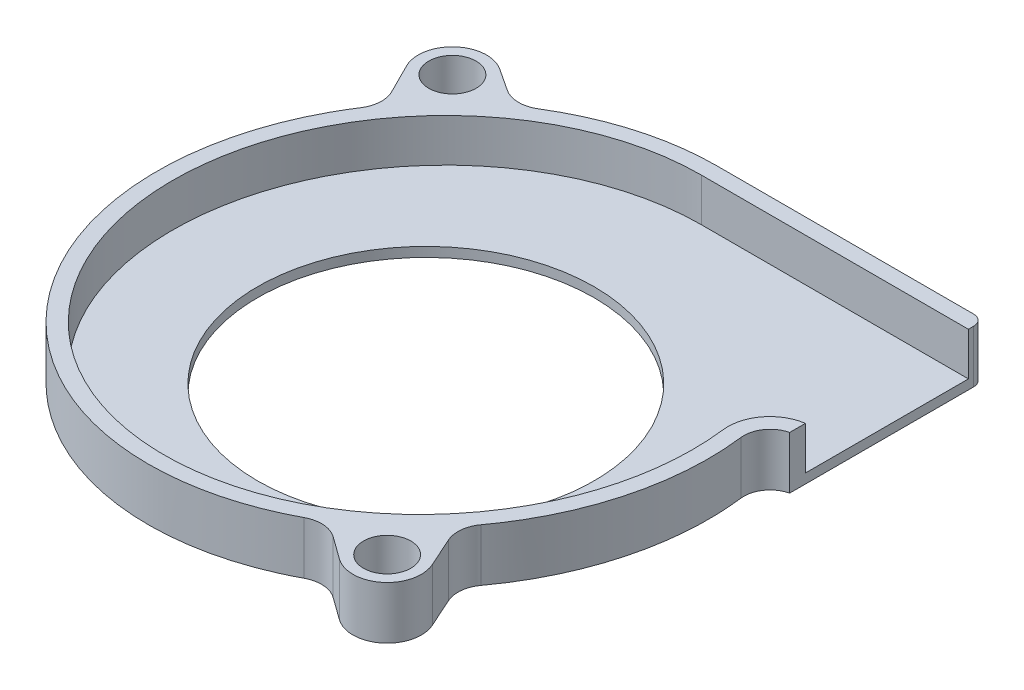
SolidWorks part; units mm, degrees
ref_plane "Front Plane" through (0, 0, 0) normal (0, 0, 1) x (1, 0, 0)
ref_plane "Top Plane" through (0, 0, 0) normal (0, 1, 0) x (1, 0, 0)
ref_plane "Right Plane" through (0, 0, 0) normal (1, 0, 0) x (0, 0, -1)
sketch "Sketch19" plane through (101.6679, 0, -9.2414) normal (0, 1, 0) x (-1, 0, 0)
  line L180 (73.5095, 9.2414) -> (95.2051, 9.2414)
  line L186 (79.9167, 11.9238) -> (79.5136, 11.896)
  line L187 (82.3906, 14.2171) -> (82.2795, 13.8418)
  line L188 (79.5136, 11.896) -> (76.2336, 11.896)
  line L189 (108.1308, 9.2414) -> (129.8264, 9.2414)
  line L190 (99.5137, 9.2414) -> (103.8222, 9.2414)
  line L191 (101.6679, 8.6855) -> (101.6679, 12.994)
  line L192 (101.6679, -18.9032) -> (101.6679, 4.3769)
  line L193 (88.3531, 30.395) -> (88.3531, 32.4937)
  line L194 (88.3531, 29.1024) -> (88.3531, 29.7557)
  line L195 (88.3531, 26.3644) -> (88.3531, 28.4631)
  line L196 (89.326, 29.4221) -> (91.4108, 29.4221)
  line L197 (88.0335, 29.4221) -> (88.6728, 29.4221)
  line L198 (85.2954, 29.4221) -> (87.3802, 29.4221)
  line L199 (117.3872, -12.6488) -> (117.3872, -10.5501)
  line L200 (117.3872, -13.9414) -> (117.3872, -13.2882)
  line L201 (117.3872, -16.6794) -> (117.3872, -14.5807)
  line L202 (118.3462, -13.6217) -> (120.4449, -13.6217)
  line L203 (117.0536, -13.6217) -> (117.7069, -13.6217)
  line L204 (114.3156, -13.6217) -> (116.4143, -13.6217)
  line L205 (100.3893, 23.6264) -> (100.3198, 24.2935)
  line L206 (98.8882, 23.4179) -> (98.7492, 24.0712)
  line L207 (97.4289, 23.0427) -> (97.2204, 23.682)
  line L208 (96.0112, 22.5284) -> (95.7333, 23.14)
  line L209 (94.6492, 21.8613) -> (94.3156, 22.445)
  line L210 (93.3705, 21.0552) -> (92.9674, 21.5972)
  line L211 (92.1752, 20.124) -> (91.7305, 20.6243)
  line L212 (91.0911, 19.0677) -> (90.5908, 19.5263)
  line L213 (90.1182, 17.9141) -> (89.5762, 18.3033)
  line L214 (89.2843, 16.6632) -> (88.7006, 16.9968)
  line L215 (88.5755, 15.329) -> (87.964, 15.593)
  line L216 (88.0057, 13.9252) -> (87.3802, 14.1337)
  line L217 (87.6026, 12.4659) -> (86.9494, 12.6049)
  line L218 (87.3385, 10.9787) -> (86.6714, 11.0482)
  line L219 (87.2412, 9.4777) -> (86.5602, 9.4777)
  line L220 (87.2968, 7.9627) -> (86.6297, 7.8932)
  line L221 (87.5053, 6.4617) -> (86.8521, 6.3227)
  line L222 (87.8667, 5.0023) -> (87.2412, 4.7939)
  line L223 (88.3948, 3.5847) -> (87.7833, 3.3067)
  line L224 (89.0619, 2.2226) -> (88.4782, 1.8891)
  line L225 (89.8542, 0.944) -> (89.3121, 0.5548)
  line L226 (90.7854, -0.2374) -> (90.2989, -0.6961)
  line L227 (91.8417, -1.3215) -> (91.3969, -1.8219)
  line L228 (93.0091, -2.2944) -> (92.6061, -2.8364)
  line L229 (94.26, -3.1422) -> (93.9264, -3.726)
  line L230 (95.5943, -3.851) -> (95.3163, -4.4626)
  line L231 (96.998, -4.407) -> (96.7895, -5.0463)
  line L232 (98.4435, -4.8239) -> (98.3045, -5.4772)
  line L233 (99.9306, -5.088) -> (99.8611, -5.7551)
  line L234 (101.4456, -5.1853) -> (101.4456, -5.8524)
  line L235 (102.9605, -5.1297) -> (103.03, -5.7968)
  line L236 (104.4476, -4.9212) -> (104.5866, -5.5745)
  line L237 (105.9209, -4.546) -> (106.1294, -5.1853)
  line L238 (107.3385, -4.0317) -> (107.6026, -4.6433)
  line L239 (108.6867, -3.3646) -> (109.0203, -3.9483)
  line L240 (109.9654, -2.5585) -> (110.3684, -3.1005)
  line L241 (111.1606, -1.6273) -> (111.6054, -2.1276)
  line L242 (112.2447, -0.571) -> (112.7451, -1.0296)
  line L243 (113.2176, 0.5826) -> (113.7597, 0.1934)
  line L244 (114.0515, 1.8335) -> (114.6353, 1.4999)
  line L245 (114.7604, 3.1677) -> (115.3719, 2.9037)
  line L246 (115.3302, 4.5715) -> (115.9696, 4.363)
  line L247 (115.7472, 6.0308) -> (116.4004, 5.8918)
  line L248 (115.9973, 7.518) -> (116.6645, 7.4485)
  line L249 (116.1085, 9.019) -> (116.7757, 9.019)
  line L250 (116.0529, 10.534) -> (116.7201, 10.6035)
  line L251 (115.8306, 12.0211) -> (116.4977, 12.174)
  line L252 (115.4692, 13.4944) -> (116.1085, 13.7028)
  line L253 (114.955, 14.912) -> (115.5665, 15.19)
  line L254 (114.2878, 16.2741) -> (114.8577, 16.6076)
  line L255 (113.4817, 17.5527) -> (114.0238, 17.9419)
  line L256 (112.5505, 18.7341) -> (113.0509, 19.1789)
  line L257 (111.4942, 19.8182) -> (111.939, 20.3185)
  line L258 (110.3406, 20.7911) -> (110.7298, 21.3331)
  line L259 (109.0759, 21.6389) -> (109.4233, 22.2088)
  line L260 (107.7416, 22.3477) -> (108.0196, 22.9593)
  line L261 (106.3517, 22.9037) -> (106.5463, 23.543)
  line L262 (104.8924, 23.3206) -> (105.0314, 23.9739)
  line L263 (103.4053, 23.5847) -> (103.4747, 24.2379)
  line L264 (101.8903, 23.682) -> (101.8903, 24.3491)
  line L265 (116.7479, 10.1587) -> (116.7757, 9.2414)
  line L266 (116.6645, 11.0621) -> (116.7479, 10.1587)
  line L267 (116.5255, 11.9655) -> (116.6645, 11.0621)
  line L268 (100.7645, 24.3213) -> (101.6679, 24.3491)
  line L269 (99.8472, 24.2379) -> (100.7645, 24.3213)
  line L270 (86.588, 10.1587) -> (86.6714, 11.0621)
  line L271 (86.5602, 9.2414) -> (86.588, 10.1587)
  line L272 (86.588, 8.338) -> (86.5602, 9.2414)
  line L273 (86.6714, 7.4207) -> (86.588, 8.338)
  line L274 (101.6679, -5.8524) -> (100.7645, -5.8246)
  line L275 (102.5852, -5.8246) -> (101.6679, -5.8524)
  line L276 (116.6645, 7.4207) -> (116.5255, 6.5312)
  line L277 (116.7479, 8.338) -> (116.6645, 7.4207)
  line L278 (116.7757, 9.2414) -> (116.7479, 8.338)
  line L279 (116.0807, 10.117) -> (116.1085, 9.2414)
  line L280 (115.9973, 10.9926) -> (116.0807, 10.117)
  line L281 (115.8723, 11.8543) -> (115.9973, 10.9926)
  line L282 (100.7923, 23.6542) -> (101.6679, 23.682)
  line L283 (99.9306, 23.5708) -> (100.7923, 23.6542)
  line L284 (87.2551, 10.117) -> (87.3385, 10.9926)
  line L285 (87.2273, 9.2414) -> (87.2551, 10.117)
  line L286 (87.2551, 8.3797) -> (87.2273, 9.2414)
  line L287 (87.3385, 7.5041) -> (87.2551, 8.3797)
  line L288 (101.6679, -5.1853) -> (100.7923, -5.1575)
  line L289 (102.5435, -5.1575) -> (101.6679, -5.1853)
  line L290 (115.9973, 7.5041) -> (115.8723, 6.6424)
  line L291 (116.0807, 8.3797) -> (115.9973, 7.5041)
  line L292 (116.1085, 9.2414) -> (116.0807, 8.3797)
  line L293 (111.9668, 9.978) -> (111.9946, 9.2414)
  line L294 (111.8834, 10.7146) -> (111.9668, 9.978)
  line L295 (111.7583, 11.4374) -> (111.8834, 10.7146)
  line L296 (100.9313, 19.5402) -> (101.6679, 19.568)
  line L297 (100.1947, 19.4707) -> (100.9313, 19.5402)
  line L298 (91.3691, 9.978) -> (91.4525, 10.7146)
  line L299 (91.3413, 9.2414) -> (91.3691, 9.978)
  line L300 (91.3691, 8.5048) -> (91.3413, 9.2414)
  line L301 (91.4525, 7.7821) -> (91.3691, 8.5048)
  line L302 (101.6679, -1.0713) -> (100.9313, -1.0435)
  line L303 (102.4046, -1.0435) -> (101.6679, -1.0713)
  line L304 (111.8834, 7.7821) -> (111.7583, 7.0593)
  line L305 (111.9668, 8.5048) -> (111.8834, 7.7821)
  line L306 (111.9946, 9.2414) -> (111.9668, 8.5048)
  line L307 (98.6797, 31.9099) -> (105.8375, 32.2852)
  line L308 (100.5838, 31.4096) -> (100.5561, 32.0211)
  line L309 (103.989, 31.6737) -> (103.9612, 32.1879)
  line L310 (105.8375, 32.2852) -> (105.8792, 31.5903)
  line L311 (98.7214, 31.0482) -> (98.6797, 31.9099)
  line L312 (86.2961, 22.8481) -> (86.9494, 23.682)
  line L313 (82.3906, 14.2171) -> (82.6269, 15.2595)
  line L314 (87.1856, 24.0156) -> (86.9494, 23.682)
  line L315 (86.7131, 27.7265) -> (86.9911, 27.4207)
  line L316 (90.6325, 30.2838) -> (90.3962, 30.6174)
  line L317 (94.2739, 29.436) -> (93.8986, 29.297)
  line L318 (90.1877, 30.9231) -> (90.3962, 30.6174)
  line L319 (86.7131, 27.7265) -> (86.4768, 27.9906)
  line L320 (90.1043, 29.7418) -> (90.1321, 29.4221)
  line L321 (90.0209, 30.0336) -> (90.1043, 29.7418)
  line L322 (86.588, 29.4221) -> (86.6158, 29.7418)
  line L323 (86.6158, 29.1163) -> (86.588, 29.4221)
  line L324 (90.1043, 29.1163) -> (90.0209, 28.8245)
  line L325 (90.1321, 29.4221) -> (90.1043, 29.1163)
  line L326 (115.2051, -14.678) -> (115.4414, -14.9699)
  line L327 (111.7166, -13.997) -> (112.0641, -13.858)
  line L328 (120.153, -7.4091) -> (119.3747, -8.2986)
  line L329 (125.6429, 4.1545) -> (125.3928, 3.0009)
  line L330 (119.1384, -8.5904) -> (119.3747, -8.2986)
  line L331 (119.2357, -12.1485) -> (119.0272, -11.8427)
  line L332 (115.6777, -15.2618) -> (115.4414, -14.9699)
  line L333 (119.2357, -12.1485) -> (119.4442, -12.4681)
  line L334 (119.1245, -13.316) -> (119.1523, -13.6217)
  line L335 (119.0411, -13.0102) -> (119.1245, -13.316)
  line L336 (115.6082, -13.6217) -> (115.636, -13.316)
  line L337 (115.636, -13.9275) -> (115.6082, -13.6217)
  line L338 (119.1245, -13.9275) -> (119.0411, -14.2194)
  line L339 (119.1523, -13.6217) -> (119.1245, -13.9275)
  line L340 (82.9466, 18.4283) -> (81.6262, 13.3137)
  line L341 (82.9883, 16.4825) -> (82.474, 16.6076)
  line L342 (82.5713, 15.0093) -> (82.0988, 15.1344)
  line L343 (81.6262, 13.3137) -> (81.9737, 13.2303)
  line L344 (83.6554, 18.2477) -> (82.9466, 18.4283)
  line L345 (126.6992, 13.411) -> (126.6992, 6.2393)
  line L346 (126.1294, 11.5347) -> (126.6992, 11.5347)
  line L347 (126.1711, 8.1156) -> (126.6992, 8.1156)
  line L348 (126.6992, 6.2393) -> (125.9904, 6.2393)
  line L349 (125.907, 13.411) -> (126.6992, 13.411)
  line L350 (90.7715, -16.5126) -> (83.5998, -16.5126)
  line L351 (88.8952, -16.0262) -> (88.8952, -16.5126)
  line L352 (85.49, -16.0262) -> (85.49, -16.5126)
  line L353 (83.5998, -16.5126) -> (83.5998, -16.0262)
  line L354 (90.7715, -16.0262) -> (90.7715, -16.5126)
  line L355 (119.7222, 25.8224) -> (120.5422, 25.0441)
  line L356 (94.2739, 29.436) -> (95.3163, 29.9086)
  line L357 (76.2336, -15.2479) -> (76.2336, 11.896)
  line L358 (76.2614, -15.4424) -> (76.2336, -15.2479)
  line L359 (76.3309, -15.637) -> (76.2614, -15.4424)
  line L360 (76.456, -15.8038) -> (76.3309, -15.637)
  line L361 (76.6227, -15.9289) -> (76.456, -15.8038)
  line L362 (76.8173, -15.9984) -> (76.6227, -15.9289)
  line L363 (77.0119, -16.0262) -> (76.8173, -15.9984)
  line L364 (103.7666, -16.0262) -> (77.0119, -16.0262)
  line L365 (104.6283, -15.9984) -> (103.7666, -16.0262)
  line L366 (105.49, -15.9289) -> (104.6283, -15.9984)
  line L367 (110.7854, -14.4278) -> (109.8264, -14.817)
  line L368 (111.7166, -13.997) -> (110.7854, -14.4278)
  line L369 (125.8514, 5.2664) -> (125.6429, 4.1545)
  line L370 (120.5422, 25.0441) -> (121.1676, 24.3908)
  spline S28 degree 3 poles (82.2795, 13.8418) (82.1213, 13.5208) (81.8076, 12.8842) (80.9543, 12.1818) (80.2645, 12.0103) (79.9167, 11.9238) knots 0 0 0 0 0.335193 0.664797 1 1 1 1
  spline S29 degree 3 poles (101.6679, 24.3491) (104.0069, 24.0252) (108.6295, 23.3848) (114.3269, 18.6424) (115.7868, 14.2088) (116.5255, 11.9655) knots 0 0 0 0 0.335972 0.664018 1 1 1 1
  spline S30 degree 3 poles (86.6714, 11.0621) (87.2366, 13.2458) (88.355, 17.5661) (93.3409, 22.5601) (97.6629, 23.6747) (99.8472, 24.2379) knots 0 0 0 0 0.335761 0.664295 1 1 1 1
  spline S31 degree 3 poles (100.7645, -5.8246) (98.4503, -5.3637) (93.8723, -4.4518) (88.48, 0.6318) (87.2787, 5.141) (86.6714, 7.4207) knots 0 0 0 0 0.335739 0.664168 1 1 1 1
  spline S32 degree 3 poles (116.5255, 6.5312) (115.8334, 4.3849) (114.4633, 0.1363) (109.1811, -4.5461) (104.7988, -5.3956) (102.5852, -5.8246) knots 0 0 0 0 0.335641 0.664413 1 1 1 1
  spline S33 degree 3 poles (101.6679, 23.682) (103.9054, 23.3721) (108.3203, 22.7605) (113.7584, 18.2278) (115.1613, 13.998) (115.8723, 11.8543) knots 0 0 0 0 0.336336 0.663662 1 1 1 1
  spline S34 degree 3 poles (87.3385, 10.9926) (87.8783, 13.0779) (88.947, 17.2069) (93.7146, 21.9749) (97.8452, 23.0354) (99.9306, 23.5708) knots 0 0 0 0 0.335633 0.664571 1 1 1 1
  spline S35 degree 3 poles (100.7923, -5.1575) (98.5828, -4.7133) (94.2132, -3.8348) (89.057, 1.0146) (87.9157, 5.3244) (87.3385, 7.5041) knots 0 0 0 0 0.335787 0.664078 1 1 1 1
  spline S36 degree 3 poles (115.8723, 6.6424) (115.2066, 4.5932) (113.8893, 0.5378) (108.8443, -3.9341) (104.6584, -4.7469) (102.5435, -5.1575) knots 0 0 0 0 0.335708 0.664385 1 1 1 1
  spline S37 degree 3 poles (101.6679, 19.568) (103.228, 19.3569) (106.3141, 18.9394) (110.1593, 15.8464) (111.2213, 12.9179) (111.7583, 11.4374) knots 0 0 0 0 0.335769 0.664184 1 1 1 1
  spline S38 degree 3 poles (91.4525, 10.7146) (91.8473, 12.1526) (92.6277, 14.9948) (95.9245, 18.2679) (98.7596, 19.0665) (100.1947, 19.4707) knots 0 0 0 0 0.335838 0.663808 1 1 1 1
  spline S39 degree 3 poles (100.9313, -1.0435) (99.3926, -0.723) (96.3435, -0.0878) (92.7284, 3.2707) (91.8804, 6.2689) (91.4525, 7.7821) knots 0 0 0 0 0.335364 0.664577 1 1 1 1
  spline S40 degree 3 poles (111.7583, 7.0593) (111.2607, 5.6562) (110.2741, 2.8742) (106.7592, -0.1744) (103.8644, -0.7521) (102.4046, -1.0435) knots 0 0 0 0 0.3353 0.664782 1 1 1 1
  spline S41 degree 3 poles (82.6269, 15.2595) (82.9027, 16.1601) (83.4547, 17.963) (84.6972, 20.5167) (85.7635, 22.0714) (86.2961, 22.8481) knots 0 0 0 0 0.333132 0.666848 1 1 1 1
  spline S42 degree 3 poles (86.9911, 27.4207) (87.1995, 27.074) (87.6163, 26.3808) (87.7039, 25.1152) (87.3583, 24.382) (87.1856, 24.0156) knots 0 0 0 0 0.333613 0.667008 1 1 1 1
  spline S43 degree 3 poles (93.8986, 29.297) (93.5019, 29.2146) (92.707, 29.0495) (91.4909, 29.4223) (90.9183, 29.9969) (90.6325, 30.2838) knots 0 0 0 0 0.332897 0.666933 1 1 1 1
  spline S44 degree 3 poles (86.4768, 27.9906) (86.1885, 28.8219) (85.6369, 30.4125) (88.0271, 32.3046) (89.4462, 31.3972) (90.1877, 30.9231) knots 0 0 0 0 0.343302 0.656868 1 1 1 1
  spline S45 degree 3 poles (86.6158, 29.7418) (86.8446, 30.2312) (87.2875, 31.1785) (89.1095, 31.3307) (89.7103, 30.4757) (90.0209, 30.0336) knots 0 0 0 0 0.340481 0.658978 1 1 1 1
  spline S46 degree 3 poles (90.0209, 28.8245) (89.7109, 28.3825) (89.1105, 27.5268) (87.2866, 27.6775) (86.8442, 28.6264) (86.6158, 29.1163) knots 0 0 0 0 0.340673 0.659593 1 1 1 1
  spline S47 degree 3 poles (112.0641, -13.858) (112.441, -13.7794) (113.1871, -13.6238) (114.3407, -13.9227) (114.915, -14.4245) (115.2051, -14.678) knots 0 0 0 0 0.335636 0.664286 1 1 1 1
  spline S48 degree 3 poles (125.3928, 3.0009) (125.0296, 1.749) (124.3006, -0.7644) (122.5332, -4.2934) (120.9444, -6.3732) (120.153, -7.4091) knots 0 0 0 0 0.332521 0.667547 1 1 1 1
  spline S49 degree 3 poles (119.0272, -11.8427) (118.8653, -11.4887) (118.5486, -10.7962) (118.5971, -9.6046) (118.9553, -8.9336) (119.1384, -8.5904) knots 0 0 0 0 0.338158 0.661533 1 1 1 1
  spline S50 degree 3 poles (119.4442, -12.4681) (119.6189, -13.254) (119.9552, -14.7658) (117.7357, -16.4106) (116.3823, -15.6551) (115.6777, -15.2618) knots 0 0 0 0 0.341627 0.657242 1 1 1 1
  spline S51 degree 3 poles (115.636, -13.316) (115.865, -12.8234) (116.3062, -11.8746) (118.1297, -11.7064) (118.7298, -12.5648) (119.0411, -13.0102) knots 0 0 0 0 0.341897 0.65855 1 1 1 1
  spline S52 degree 3 poles (119.0411, -14.2194) (118.7323, -14.663) (118.1357, -15.52) (116.3165, -15.3612) (115.8684, -14.4173) (115.636, -13.9275) knots 0 0 0 0 0.340624 0.657859 1 1 1 1
  spline S53 degree 3 poles (95.3163, 29.9086) (98.1066, 30.7198) (103.6867, 32.3422) (112.6245, 30.9005) (117.3564, 27.515) (119.7222, 25.8224) knots 0 0 0 0 0.333391 0.66672 1 1 1 1
  spline S54 degree 3 poles (109.8264, -14.817) (109.3624, -14.9921) (108.4256, -15.3457) (106.9748, -15.7324) (105.9817, -15.8638) (105.49, -15.9289) knots 0 0 0 0 0.331237 0.668901 1 1 1 1
  spline S55 degree 3 poles (121.1676, 24.3908) (122.4335, 22.5329) (124.9882, 18.7834) (126.4142, 12.0045) (126.0381, 7.5014) (125.8514, 5.2664) knots 0 0 0 0 0.330973 0.667942 1 1 1 1
sketch "Sketch18" plane through (0, 0, 0) normal (0, 1, 0) x (1, 0, 0)
  line L0 (-23.0057, 21.1739) -> (-21.5825, 18.3332)
  line L1 (14.4232, -22.6366) -> (12.2821, -21.0936)
  line L2 (-18.3115, 25.3434) -> (-16.2051, 23.9551)
  line L3 (-16.9421, 19.0744) -> (0, 0) construction
  line L4 (16.3234, -20) -> (0, 0) construction
  line L5 (-33.0815, -23.9) -> (4.114, -23.9) construction
  line L6 (-26.2, -10.7544) -> (-26.2, -0.8211) construction
  line L7 (0, 0) -> (0, -6.8242) construction
  line L8 (-4, 0) -> (-4, -27.6209) construction
  line L9 (4, 0) -> (4, -27.6209) construction
  line L10 (0, 0) -> (0, 25.466) construction
  line L11 (0.75, 0) -> (0.75, 25.466) construction
  line L12 (-0.75, 0) -> (-0.75, 25.466) construction
  line L13 (-12.8119, -19.8447) -> (10.3119, 23.6447) construction
  line L14 (-21.6522, 12.748) -> (19.1522, -8.948) construction
  line L15 (-1.25, 1.9) -> (3.3669, 1.9) construction
  line L16 (0, 0) -> (21.8429, 12.611) construction
  line L17 (0, 0) -> (-26.1434, 15.0939) construction
  line L18 (0, 0) -> (-23.531, -13.5856) construction
  line L19 (-0.0106, 27.7) -> (24.4, 27.7)
  line L20 (0, 0) -> (22.2135, -12.825) construction
  line L21 (0, 0) -> (6.1332, 0) construction
  line L22 (4, 0) -> (4, -6.8242) construction
  line L23 (-4, 0) -> (-4, -6.8242) construction
  line L24 (-1.5, 0) -> (-26.5184, 14.4444) construction
  line L25 (-1.5, 0) -> (-23.906, -12.9361) construction
  line L26 (25.4, 26.7) -> (25.4, 9.2)
  line L27 (25.4, 9.2) -> (23.0016, 9.2)
  line L28 (1.5, 0) -> (-25.7684, 15.7434) construction
  line L29 (1.5, 0) -> (-23.156, -14.2351) construction
  line L30 (9.3582, -4.5369) -> (22.5885, -12.1755) construction
  line L31 (19.2873, -18.6667) -> (18.0311, -15.874)
  line L157 (8.6082, -5.836) -> (21.8385, -13.4745) construction
  line L159 (9.3582, 4.5369) -> (22.2179, 11.9615) construction
  line L161 (8.6082, 5.836) -> (21.4679, 13.2605) construction
  line L164 (11.0633, 27.6622) -> (11.0633, 28.1486) construction
  line L165 (18.2349, 28.1486) -> (18.2349, 27.6622) construction
  line L166 (16.3586, 27.6622) -> (16.3586, 28.1486) construction
  line L167 (12.9535, 27.6622) -> (12.9535, 28.1486) construction
  line L168 (11.0633, 28.1486) -> (18.2349, 28.1486) construction
  line L169 (-26.0052, -3.975) -> (-26.3506, -3.975) construction
  line L170 (-26.3506, 3.1828) -> (-25.7716, 3.1828) construction
  line L171 (-26.1178, 1.3065) -> (-26.3506, 1.3065) construction
  line L172 (-26.0193, -2.0987) -> (-26.3506, -2.0987) construction
  line L173 (-26.3506, -3.975) -> (-26.3506, 3.1828) construction
  line L174 (19.9063, -12.0569) -> (20.36, -12.2293) construction
  line L175 (22.6116, -6.1418) -> (22.2945, -6.0236) construction
  line L176 (21.4807, -7.7289) -> (21.9583, -7.9069) construction
  line L177 (20.6345, -10.3321) -> (21.0132, -10.4642) construction
  line L178 (20.36, -12.2293) -> (22.6116, -6.1418) construction
  circle A0 centre (16.3234, -20) radius 2.25
  arc A1 (19.2873, -18.6667) -> (14.4232, -22.6366) centre (16.3234, -20) ccw construction
  circle A2 centre (-20.1, 22.6298) radius 2.25
  arc A3 (-18.3115, 25.3434) -> (-23.0057, 21.1739) centre (-20.1, 22.6298) ccw
  circle A4 centre (0, 0) radius 9.2 construction
  arc A5 (-16.2051, 23.9551) -> (-13.1979, 23.9077) centre (-14.6643, 26.293) ccw
  arc A6 (-21.5825, 18.3332) -> (-21.7386, 15.5524) centre (-24.0858, 17.079) cw
  arc A7 (-23.0057, 21.1739) -> (-18.3115, 25.3434) centre (-20.1, 22.6298) ccw construction
  arc A8 (12.2821, -21.0936) -> (9.3249, -20.8959) centre (10.6451, -23.3651) ccw
  arc A9 (25.4, 26.7) -> (24.4, 27.7) centre (24.4, 26.7) ccw
  circle A10 centre (0, 0) radius 10.4 construction
  arc A11 (18.0311, -15.874) -> (18.3294, -13.0658) centre (20.5846, -14.7253) cw
  arc A12 (14.4232, -22.6366) -> (19.2873, -18.6667) centre (16.3234, -20) ccw
  circle A13 centre (0, 0) radius 16
  ellipse E0 centre (-1.25, 1.9) end of major axis (10.3119, 23.6447) minor radius 23.1069 construction
  ellipse E1 centre (-1.25, 1.9) end of major axis (-13.5161, -21.1691) minor radius 24.6069 (-21.7386, 15.5524) -> (9.3249, -20.8959) ccw
  ellipse E2 centre (-1.25, 1.9) end of major axis (-13.5161, -21.1691) minor radius 24.6069 (-0.0106, 27.7) -> (-13.1979, 23.9077) ccw
  ellipse E3 centre (-1.25, 1.9) end of major axis (-13.5161, -21.1691) minor radius 24.6069 (23.0016, 9.2) -> (-0.0106, 27.7) ccw construction
  ellipse E4 centre (-1.25, 1.9) end of major axis (-13.5161, -21.1691) minor radius 24.6069 (18.3294, -13.0658) -> (23.0016, 9.2) ccw
  dimension "D1" = 6.5
  dimension "D2" = 4.5
  dimension "D4" = 32
  dimension "D5" = 2.8
  dimension "D7" = 0.75
  dimension "D8" = 1
  dimension "D16" = 18.4
  dimension "D34" = 15
  dimension "D6" = 15
  dimension "D9" = 16.3234
  dimension "D10" = 20.1
  dimension "D11" = 25.4
  dimension "D12" = 27.7
  dimension "D13" = 51.6
  dimension "D14" = 20
  dimension "D15" = 51.6
  dimension "D21" = 17.5
  dimension "D22" = 28
  dimension "D23" = 0.75
  dimension "D24" = 1.9
  dimension "D25" = 1.25
  dimension "D26" = 1.5
  dimension "D27" = 1.5
  dimension "D28" = 30
  dimension "D29" = 30
  dimension "D30" = 30
  dimension "D31" = 30
  dimension "D33" = 48.388
  dimension "D17" = 4
  dimension "D18" = 4
  dimension "D19" = 1.2
  dimension "D20" = 0.75
  dimension "D32" = 0.75
extrude "Boss-Extrude2" add sketch "Sketch18" along normal blind 0.91
fillet "Fillet1" radius 2.5 1 edges at (23.0016, 0.455, -9.2)
sketch "Sketch22" plane through (0, 0.91, 0) normal (0, -1, 0) x (-1, 0, 0)
  line L0 (0.0106, 27.7) -> (-24.4, 27.7) construction
  line L1 (-25.4, 26.7) -> (-25.4, 9.2) construction
  line L3 (-19.2873, -18.6667) -> (-18.0311, -15.874) construction
  line L4 (-23.0016, 9.2) -> (-18.3294, -13.0658) construction
  line L5 (-21.7837, 10.7) -> (-16.9208, -12.4744) construction
  line L6 (13.1979, 23.9077) -> (0.0106, 27.7) construction
  line L7 (12.608, 22.5165) -> (-0.2008, 26.2) construction
  line L8 (-9.3249, -20.8959) -> (21.7386, 15.5524) construction
  line L9 (-9.8059, -19.1478) -> (19.98, 15.8015) construction
  line L10 (-25.4, 9.2) -> (-23.0016, 9.2) construction
  line L13 (-14.4232, -22.6366) -> (-12.2821, -21.0936) construction
  line L14 (23.0057, 21.1739) -> (21.5825, 18.3332) construction
  line L15 (18.3115, 25.3434) -> (16.2051, 23.9551) construction
  line L16 (0.0106, 27.7) -> (-24.4, 27.7)
  line L17 (-25.4, 26.7) -> (-25.4, 26.2)
  line L20 (-19.2873, -18.6667) -> (-18.0311, -15.874)
  line L21 (-14.4232, -22.6366) -> (-12.2821, -21.0936)
  line L22 (23.0057, 21.1739) -> (21.5825, 18.3332)
  line L23 (18.3115, 25.3434) -> (16.2051, 23.9551)
  line L24 (-25.4, 10.7) -> (-25.4, 9.2)
  line L30 (-0.0142, 26.2) -> (-25.4, 26.2)
  line L31 (-0.2008, 26.2) -> (-23.9, 26.2) construction
  line L32 (-23.9, 26.2) -> (-23.9, 10.7) construction
  line L33 (-23.9, 10.7) -> (-21.7837, 10.7) construction
  line L34 (-25.4, 26.7) -> (-25.4, 9.2) construction
  line L35 (19.137, 24.0909) -> (17.0306, 22.7027) construction
  line L36 (21.6646, 21.8459) -> (20.2414, 19.0052) construction
  line L37 (-17.9194, -19.2821) -> (-16.6631, -16.4894) construction
  line L38 (-15.3002, -21.4197) -> (-13.1592, -19.8767) construction
  arc A1 (-23.4964, 6.4567) -> (-25.4, 9.2) centre (-25.977, 6.7675) ccw construction
  arc A2 (-24.4, 27.7) -> (-25.4, 26.7) centre (-24.4, 26.7) ccw construction
  arc A3 (-18.0311, -15.874) -> (-18.3294, -13.0658) centre (-20.5846, -14.7253) ccw construction
  arc A4 (-19.2873, -18.6667) -> (-14.4232, -22.6366) centre (-16.3234, -20) ccw construction
  arc A5 (-9.3249, -20.8959) -> (-12.2821, -21.0936) centre (-10.6451, -23.3651) ccw construction
  arc A6 (-22.0099, 6.2489) -> (-25.4, 10.7) centre (-25.9793, 6.7422) ccw
  arc A7 (-23.4964, 6.4567) -> (-25.4, 9.2) centre (-25.977, 6.7675) ccw
  arc A15 (21.5825, 18.3332) -> (21.7386, 15.5524) centre (24.0858, 17.079) ccw construction
  arc A16 (23.0057, 21.1739) -> (18.3115, 25.3434) centre (20.1, 22.6298) ccw construction
  arc A17 (13.1979, 23.9077) -> (16.2051, 23.9551) centre (14.6643, 26.293) ccw construction
  arc A18 (-24.4, 27.7) -> (-25.4, 26.7) centre (-24.4, 26.7) ccw
  arc A19 (-18.0311, -15.874) -> (-18.3294, -13.0658) centre (-20.5846, -14.7253) ccw
  arc A20 (-19.2873, -18.6667) -> (-14.4232, -22.6366) centre (-16.3234, -20) ccw
  arc A21 (-9.3249, -20.8959) -> (-12.2821, -21.0936) centre (-10.6451, -23.3651) ccw
  arc A22 (21.5825, 18.3332) -> (21.7386, 15.5524) centre (24.0858, 17.079) ccw
  arc A23 (23.0057, 21.1739) -> (18.3115, 25.3434) centre (20.1, 22.6298) ccw
  arc A24 (13.1979, 23.9077) -> (16.2051, 23.9551) centre (14.6643, 26.293) ccw
  circle A25 centre (20.1, 22.6298) radius 2.25 construction
  arc A32 (-23.9, 26.2) -> (-23.9, 26.2) centre (-23.9, 26.2) ccw construction
  circle A33 centre (20.1, 22.6298) radius 2.25
  circle A34 centre (-16.3234, -20) radius 2.25 construction
  circle A35 centre (-16.3234, -20) radius 2.25
  arc A36 (21.6646, 21.8459) -> (19.137, 24.0909) centre (20.1, 22.6298) ccw construction
  arc A37 (12.608, 22.5165) -> (17.0306, 22.7027) centre (14.6643, 26.293) ccw construction
  arc A38 (20.2414, 19.0052) -> (19.98, 15.8015) centre (24.0858, 17.079) ccw construction
  arc A39 (-16.6631, -16.4894) -> (-16.9208, -12.4744) centre (-20.5846, -14.7253) ccw construction
  arc A40 (-17.9194, -19.2821) -> (-15.3002, -21.4197) centre (-16.3234, -20) ccw construction
  arc A41 (-9.8059, -19.1478) -> (-13.1592, -19.8767) centre (-10.6451, -23.3651) ccw construction
  ellipse E0 centre (1.25, 1.9) end of major axis (-10.3119, 23.6447) minor radius 23.1047 (-22.0099, 6.2489) -> (-0.0142, 26.2) ccw
  ellipse E2 centre (1.25, 1.9) end of major axis (13.5161, -21.1691) minor radius 24.6069 (-23.4964, 6.4567) -> (-18.3294, -13.0658) ccw construction
  ellipse E3 centre (1.25, 1.9) end of major axis (13.5161, -21.1691) minor radius 24.6069 (-23.4964, 6.4567) -> (-18.3294, -13.0658) ccw
  ellipse E5 centre (1.25, 1.9) end of major axis (13.5161, -21.1691) minor radius 24.6069 (-9.3249, -20.8959) -> (21.7386, 15.5524) ccw construction
  ellipse E6 centre (1.25, 1.9) end of major axis (13.5161, -21.1691) minor radius 24.6069 (13.1979, 23.9077) -> (0.0106, 27.7) ccw construction
  ellipse E8 centre (1.25, 1.9) end of major axis (13.5161, -21.1691) minor radius 24.6069 (-9.3249, -20.8959) -> (21.7386, 15.5524) ccw
  ellipse E9 centre (1.25, 1.9) end of major axis (13.5161, -21.1691) minor radius 24.6069 (13.1979, 23.9077) -> (0.0106, 27.7) ccw
  dimension "D2" = 4
  dimension "D1" = 1.5
extrude "Boss-Extrude3" add sketch "Sketch22" against normal blind 4.09
